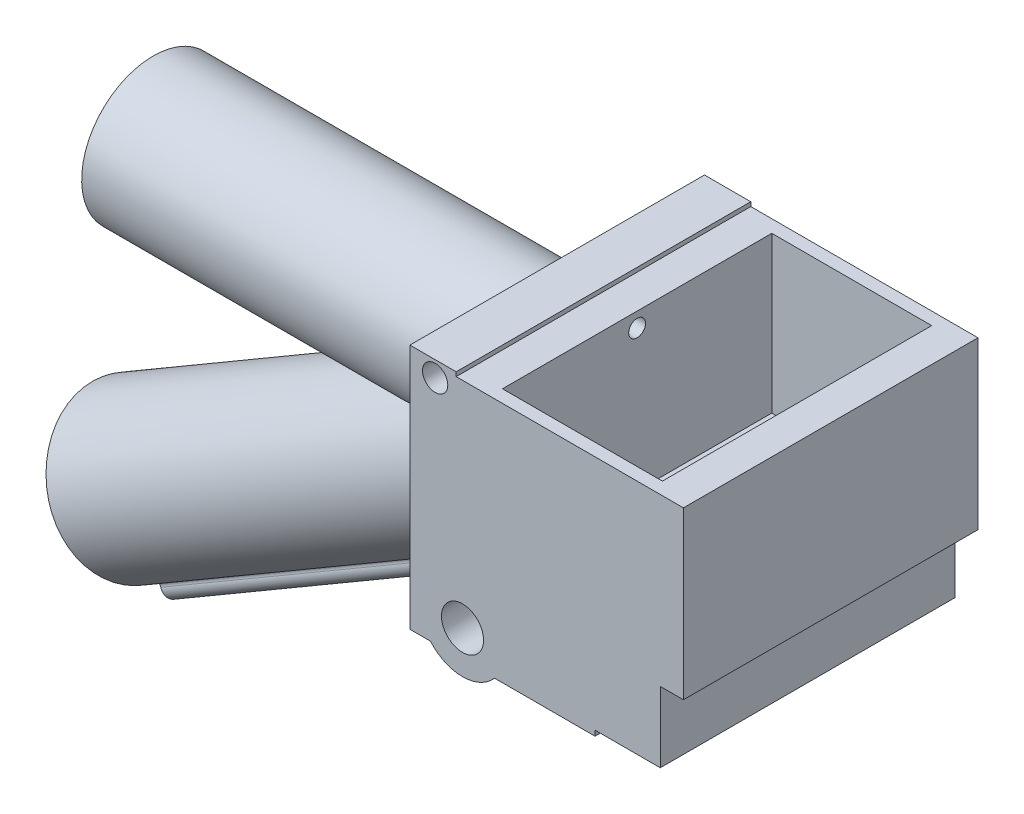
SolidWorks part; units mm, degrees
ref_plane "Plan de face" through (0, 0, 0) normal (0, 0, 1) x (1, 0, 0)
ref_plane "Plan de dessus" through (0, 0, 0) normal (0, 1, 0) x (1, 0, 0)
ref_plane "Plan de droite" through (0, 0, 0) normal (1, 0, 0) x (0, 0, -1)
sketch "Esquisse1" plane through (0, 0, 0) normal (1, 0, 0) x (0, 0, -1)
  circle A0 centre (0, 0) radius 17
  dimension "D1" = 34
extrude "Boss.-Extru.1" add sketch "Esquisse1" along normal blind 96
sketch "Esquisse2" plane through (96, 0, 0) normal (1, 0, 0) x (0, 0, -1)
  line L0 (-35, 23) -> (35, 23)
  line L1 (35, 23) -> (35, -35.5)
  line L2 (35, -35.5) -> (-35, -35.5)
  line L3 (-35, -35.5) -> (-35, 23)
  circle A0 centre (0, 0) radius 17
  point P7 (0, 23)
  dimension "D1" = 34
  dimension "D2" = 23
  dimension "D3" = 70
  dimension "D4" = 58.5
extrude "Boss.-Extru.3" add sketch "Esquisse2" along normal blind 65 contours L3 L0 L1 L2
sketch "Esquisse4" plane through (0, 0, 0) normal (0, 0, 1) x (1, 0, 0)
  line L0 (161, 0) -> (119, 0) construction
  line L1 (161, 23) -> (161, -35.5) construction
  line L2 (119, 0) -> (-5.3125, -72.6801) construction
  line L3 (-5.3125, -72.6801) -> (161, 0) construction
  line L4 (119, 0) -> (101.3985, 30.1057) construction
  dimension "D1" = 42
  dimension "D2" = 144
  dimension "D3" = 181.5
  dimension "D4" = 90
sketch3d "Esquisse3D2"
  line L0 (119, 0, 0) -> (101.3985, 30.1057, 0) construction
  line L1 (119, 0, 0) -> (-5.3125, -72.6801, 0) construction
sketch "Esquisse6" plane through (88.6853, 51.8504, 0) normal (0.8633, 0.5047, 0) x (0, 0, -1)
  line L0 (0, -60.0621) -> (0, -25.1884) construction
  circle A0 centre (0, -60.0621) radius 18
  dimension "D1" = 60.0621
  dimension "36" = 36
extrude "Boss.-Extru.4" add sketch "Esquisse6" against normal blind 144
sketch "Esquisse7" plane through (161, 0, 0) normal (1, 0, 0) x (0, 0, -1)
  line L1 (-35, -35.5) -> (-35, 23) construction
  line L2 (35, 23) -> (35, -35.5) construction
  line L5 (-35, -35.5) -> (35, -35.5)
  line L6 (-35, -35.5) -> (-35, -17.5)
  line L7 (-35, -17.5) -> (35, -17.5)
  line L8 (35, -35.5) -> (35, -17.5)
  dimension "D1" = 18
extrude "Enlèv. mat.-Extru.1" cut sketch "Esquisse7" against normal blind 5.5
sketch "Esquisse8" plane through (155.5, 0, 0) normal (1, 0, 0) x (0, 0, -1)
  line L0 (35, -35.5) -> (35, -17.5) construction
  line L1 (-35, -35.5) -> (35, -35.5)
  line L2 (-35, -35.5) -> (-35, -34.25)
  line L3 (-35, -34.25) -> (35, -34.25)
  line L4 (35, -35.5) -> (35, -34.25)
  dimension "D1" = 1.25
extrude "Enlèv. mat.-Extru.2" cut sketch "Esquisse8" against normal blind 15.5
sketch "Esquisse9" plane through (-35.6272, -20.8297, 0) normal (-0.8633, -0.5047, 0) x (0, 0, 1)
  line L0 (0, -60.0621) -> (0, -79.5621) construction
  circle A0 centre (0, -60.0621) radius 18
  circle A2 centre (0, -79.5621) radius 2.5
  dimension "D1" = 36
  dimension "D2" = 19.5
  dimension "D3" = 5
extrude "Boss.-Extru.5" add sketch "Esquisse9" against normal blind 120 contours A2
fillet "Congé1" radius 1 2 edges at (49.8604, -61.1548, -1.9188) (49.8604, -61.1548, 1.9188)
sketch "Esquisse10" plane through (0, 23, 0) normal (0, 1, 0) x (1, 0, 0)
  line L0 (161, -35) -> (96, -35) construction
  line L1 (161, 35) -> (107, 35)
  line L2 (161, 35) -> (161, -35)
  line L3 (161, -35) -> (107, -35)
  line L4 (107, 35) -> (107, -35)
  dimension "D1" = 54
extrude "Enlèv. mat.-Extru.3" cut sketch "Esquisse10" against normal blind 1
sketch "Esquisse11" plane through (0, 22, 0) normal (0, 1, 0) x (1, 0, 0)
  line L0 (0, 0) -> (161, 0) construction
  line L1 (115, 32) -> (153, 32)
  line L2 (115, 32) -> (115, -32)
  line L3 (115, -32) -> (153, -32)
  line L4 (153, 32) -> (153, -32)
  line L5 (161, -35) -> (161, 35) construction
  point P11 (115, 0)
  dimension "D1" = 38
  dimension "D2" = 64
  dimension "D3" = 8
extrude "Enlèv. mat.-Extru.4" cut sketch "Esquisse11" against normal blind 37
sketch "Esquisse17" plane through (0, 0, 35) normal (0, 0, 1) x (1, 0, 0)
  line L0 (96, 19.25) -> (102, 19.25) construction
  line L2 (96, -35.5) -> (96, 23) construction
  line L5 (102, 19.25) -> (102, 23) construction
  line L6 (107, 23) -> (96, 23) construction
  dimension "D1" = 3.75
  dimension "D2" = 6
sketch "Esquisse23" plane through (0, 0, 35) normal (0, 0, 1) x (1, 0, 0)
  point P0 (102, 19.25)
hole_wizard "Diamètre du perçage Ø6.0 (6)3" positions "Esquisse23" profile "Esquisse22" hole size "Ø6.0" standard "ISO"
sketch "Esquisse22" plane through (102, 19.25, 35) normal (1, 0, 0) x (0, -1, 0)
  line L0 (0, 0) -> (0, 39.3026)
  line L1 (0, 39.3026) -> (3, 37.5)
  line L2 (3, 37.5) -> (3, 0)
  line L5 (3, 0) -> (0, 0)
  line L10 (0, 39.3026) -> (-3, 37.5) construction
  line L11 (0, -6.35) -> (0, 107.95) construction
  dimension "Diamètre du perçage" = 6
  dimension "Profondeur du perçage" = 37.5
  dimension "Angle de pointe" = 118
sketch "Esquisse24" plane through (115, 0, 0) normal (1, 0, 0) x (0, 0, -1)
  line L0 (0, 22) -> (0, 18.5) construction
  line L1 (-35, 22) -> (35, 22) construction
  point P1 (0, 18.5)
  point P6 (0, 18.5)
  dimension "D1" = 3.5
hole_wizard "Diamètre du perçage Ø4.0 (4)1" positions "Esquisse24" profile "Esquisse25" hole size "Ø4.0" standard "ISO"
sketch "Esquisse25" plane through (115, 18.5, 0) normal (0, 1, 0) x (0, 0, -1)
  line L0 (0, 0) -> (0, 14.2017)
  line L1 (0, 14.2017) -> (2, 13)
  line L2 (2, 13) -> (2, 0)
  line L5 (2, 0) -> (0, 0)
  line L10 (0, 14.2017) -> (-2, 13) construction
  line L11 (0, -6.35) -> (0, 107.95) construction
  dimension "Diamètre du perçage" = 4
  dimension "Profondeur du perçage" = 13
  dimension "Angle de pointe" = 118
sketch "Esquisse26" plane through (0, 0, 0) normal (0, 0, 1) x (1, 0, 0)
  line L0 (161, 0) -> (108.5, 0) construction
  line L1 (161, 22) -> (161, -17.5) construction
  line L2 (108.5, 0) -> (108.5, -29) construction
  circle A0 centre (108.5, -29) radius 10
  dimension "D3" = 20
  dimension "D1" = 52.5
  dimension "D2" = 29
extrude "Boss.-Extru.6" add sketch "Esquisse26" along normal blind 35 and the other way blind 35
sketch "Esquisse27" plane through (0, -35.5, 0) normal (0, -1, 0) x (1, 0, 0)
  line L0 (140, 0) -> (130, 0) construction
  line L1 (140, -35) -> (140, 35) construction
  circle A0 centre (130, 0) radius 8
  dimension "D2" = 16
  dimension "D1" = 10
extrude "Boss.-Extru.7" add sketch "Esquisse27" along normal blind 5.5 contours A0
sketch "Esquisse33" plane through (0, -41, 0) normal (0, -1, 0) x (1, 0, 0)
  circle A0 centre (130, 0) radius 4
  dimension "D1" = 8
extrude "Enlèv. mat.-Extru.7" cut sketch "Esquisse33" against normal blind 12.5
sketch "Esquisse36" plane through (0, 0, -35) normal (0, 0, -1) x (-1, 0, 0)
  point P0 (-108.5, -29)
hole_wizard "Diamètre du perçage Ø10.0 (10)1" positions "Esquisse36" profile "Esquisse35" hole size "Ø10.0" standard "ISO"
sketch "Esquisse35" plane through (108.5, -29, -35) normal (1, 0, 0) x (0, 1, 0)
  line L0 (0, 0) -> (0, 73.0043)
  line L1 (0, 73.0043) -> (5, 70)
  line L2 (5, 70) -> (5, 0)
  line L5 (5, 0) -> (0, 0)
  line L10 (0, 73.0043) -> (-5, 70) construction
  line L11 (0, -6.35) -> (0, 107.95) construction
  dimension "Diamètre du perçage" = 10
  dimension "Profondeur du perçage" = 70
  dimension "Angle de pointe" = 118
sketch "Esquisse43" plane through (-35.6272, -20.8297, 0) normal (-0.8633, -0.5047, 0) x (0, 0, 1)
  point P0 (0, -79.5621)
hole_wizard "Trou pour taraudage pour trou taraudé M31" positions "Esquisse43" profile "Esquisse42" hole size "M3" standard "ISO"
sketch "Esquisse42" plane through (4.5296, -89.5141, 0) normal (0, 0, 1) x (0.5047, -0.8633, 0)
  line L0 (0, 0) -> (0, 6.7511)
  line L1 (0, 6.7511) -> (1.25, 6)
  line L2 (1.25, 6) -> (1.25, 0)
  line L5 (1.25, 0) -> (0, 0)
  line L10 (0, 6.7511) -> (-1.25, 6) construction
  line L11 (0, -6.35) -> (0, 107.95) construction
  dimension "Diamètre du perçage" = 2.5
  dimension "Profondeur du perçage" = 6
  dimension "Angle de pointe" = 118
fillet "Congé2" radius 2 1 edges at (130, -35.5, -8)
sketch "Esquisse47" plane through (0, 0, 0) normal (-1, 0, 0) x (0, 0, 1)
  circle A0 centre (0, 0) radius 15.5
  dimension "D1" = 31
